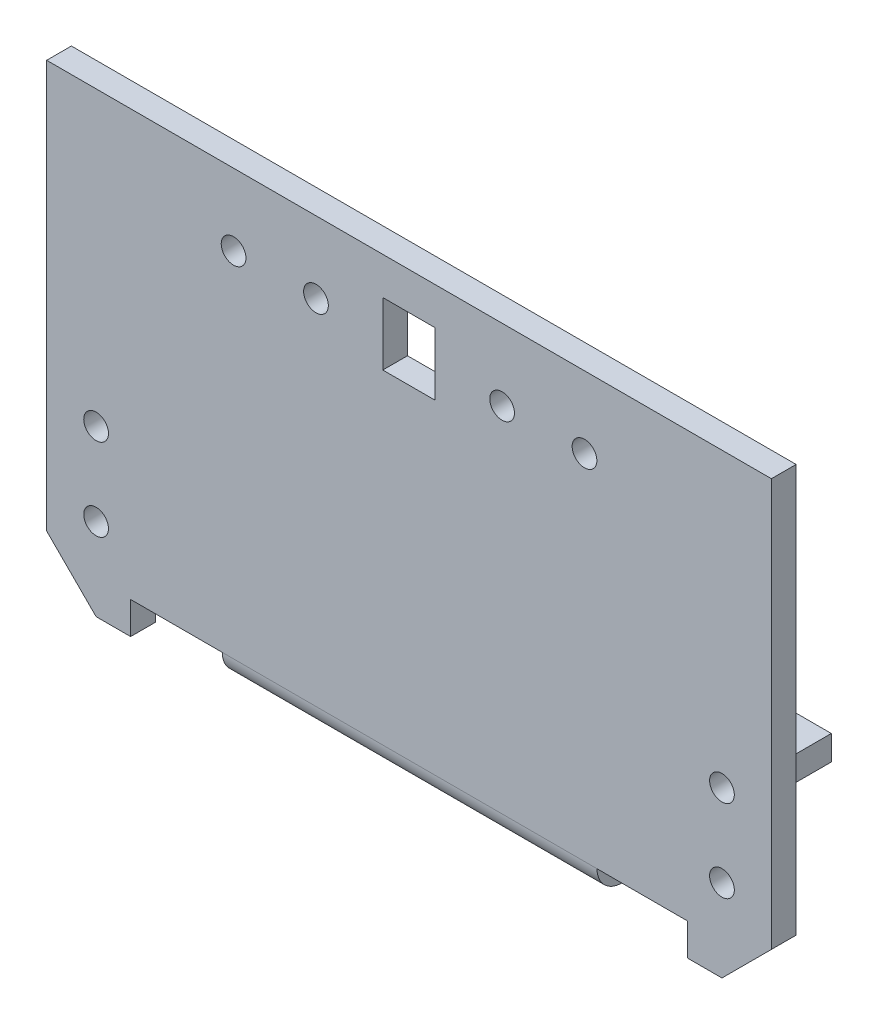
SolidWorks part; units mm, degrees
ref_plane "Front Plane" through (0, 0, 0) normal (0, 0, 1) x (1, 0, 0)
ref_plane "Top Plane" through (0, 0, 0) normal (0, 1, 0) x (1, 0, 0)
ref_plane "Right Plane" through (0, 0, 0) normal (1, 0, 0) x (0, 0, -1)
sketch "Sketch1" plane through (0, 0, 0) normal (0, 0, 1) x (1, 0, 0)
  line L1 (-33.7879, 25.3517) -> (-33.7879, 14.6993) construction
  line L2 (-33.7879, 14.6993) -> (-37.9759, 14.6993) construction
  line L3 (-37.9759, 14.6993) -> (-43.9759, 20.6993) construction
  line L4 (-43.9759, 20.6993) -> (-43.9759, 28.4551) construction
  line L7 (-33.7879, 18.6025) -> (-33.7879, 14.6993)
  line L8 (-33.7879, 14.6993) -> (-37.9759, 14.6993)
  line L9 (-37.9759, 14.6993) -> (-43.9759, 20.6993)
  line L10 (-43.9759, 20.6993) -> (-43.9759, 28.4551)
  line L11 (-43.9759, 28.4551) -> (-43.9759, 70.1751)
  line L14 (33.7879, 18.6025) -> (33.7879, 14.6993)
  line L15 (33.7879, 14.6993) -> (37.9759, 14.6993)
  line L16 (37.9759, 14.6993) -> (43.9759, 20.6993)
  line L17 (43.9759, 20.6993) -> (43.9759, 28.4551)
  line L18 (-43.9759, 70.1751) -> (43.9759, 70.1751)
  line L19 (33.7879, 18.6025) -> (-33.7879, 18.6025)
  line L21 (43.9759, 70.1751) -> (43.9759, 28.4551)
  dimension "D1" = 41.72
extrude "Boss-Extrude1" add sketch "Sketch1" along normal blind 3 contours L21 L17 L16 L15 L14 L19 L7 L8 L9 L10 L11 L18
sketch "Sketch2" plane through (0, 0, 3) normal (0, 0, 1) x (1, 0, 0)
  line L0 (37.9759, 14.6993) -> (37.9759, 24.6993) construction
  line L1 (0, 0) -> (0, 83.7503) construction
  line L3 (21.2938, 63.9782) -> (1.2938, 63.9782) construction
  line L4 (21.2938, 63.9782) -> (21.2938, 61.4782) construction
  circle A0 centre (37.9759, 24.6993) radius 1.5
  circle A2 centre (37.9759, 34.6993) radius 1.5
  circle A3 centre (-37.9759, 24.6993) radius 1.5
  circle A4 centre (-37.9759, 34.6993) radius 1.5
  circle A5 centre (21.2938, 61.4782) radius 1.5
  circle A6 centre (11.2938, 61.4782) radius 1.5
  circle A7 centre (-11.2938, 61.4782) radius 1.5
  circle A8 centre (-21.2938, 61.4782) radius 1.5
  dimension "D2" = 2
  dimension "D3" = 3
  dimension "D4" = 2.5
  dimension "D5" = 20
  dimension "D6" = 3
  dimension "D1" = 10
  dimension "D7" = 2
extrude "Cut-Extrude1" cut sketch "Sketch2" against normal up to surface (3 mm away) up to face at (0, 27.7751, 0)
sketch "Sketch3" plane through (0, 0, 0) normal (0, 0, -1) x (-1, 0, 0)
  line L0 (3.1837, 65.6365) -> (-3.1663, 65.6365)
  line L1 (-3.1663, 65.6365) -> (-3.1663, 58.0165)
  line L2 (-3.1663, 58.0165) -> (3.1837, 58.0165)
  line L3 (3.1837, 58.0165) -> (3.1837, 65.6365)
  dimension "D1" = 7.62
  dimension "D2" = 6.35
extrude "Cut-Extrude2" cut sketch "Sketch3" against normal up to surface (3 mm away) up to face at (22.7938, 61.4782, 3)
sketch "Sketch4" plane through (0, 18.6025, 0) normal (0, -1, 0) x (1, 0, 0)
  line L0 (-12.6851, -20.4341) -> (14.9476, -20.4341)
  line L1 (14.9476, -20.4341) -> (14.9476, -25.4341)
  line L2 (14.9476, -25.4341) -> (22.8153, -25.4341)
  line L3 (-22.6647, 3) -> (-22.6647, -25.4341)
  line L7 (22.8153, 3) -> (22.8153, -25.4341)
  line L12 (-12.6851, -25.4341) -> (-22.6647, -25.4341)
  line L14 (22.8153, 3) -> (-22.6647, 3)
  line L15 (-22.6647, 3) -> (22.8153, 3)
  line L19 (-12.6851, -20.4341) -> (-12.6851, -25.4341)
  line M12 (-33.7879, 0) -> (33.7879, 0)
  line M14 (33.7879, 3) -> (-33.7879, 3)
  dimension "D2" = 45.48
  dimension "D3" = 5
extrude "Boss-Extrude2" add sketch "Sketch4" along normal blind 3 contours L19 L7 L3 L12 M12 | L7 L3 M14 M12 region at (-0.068, 18.6025, -11.3312) region at (0.0753, 18.6025, 1.5)
fillet "Fillet2" radius 3 1 edges at (0.0753, 15.6025, 3)
